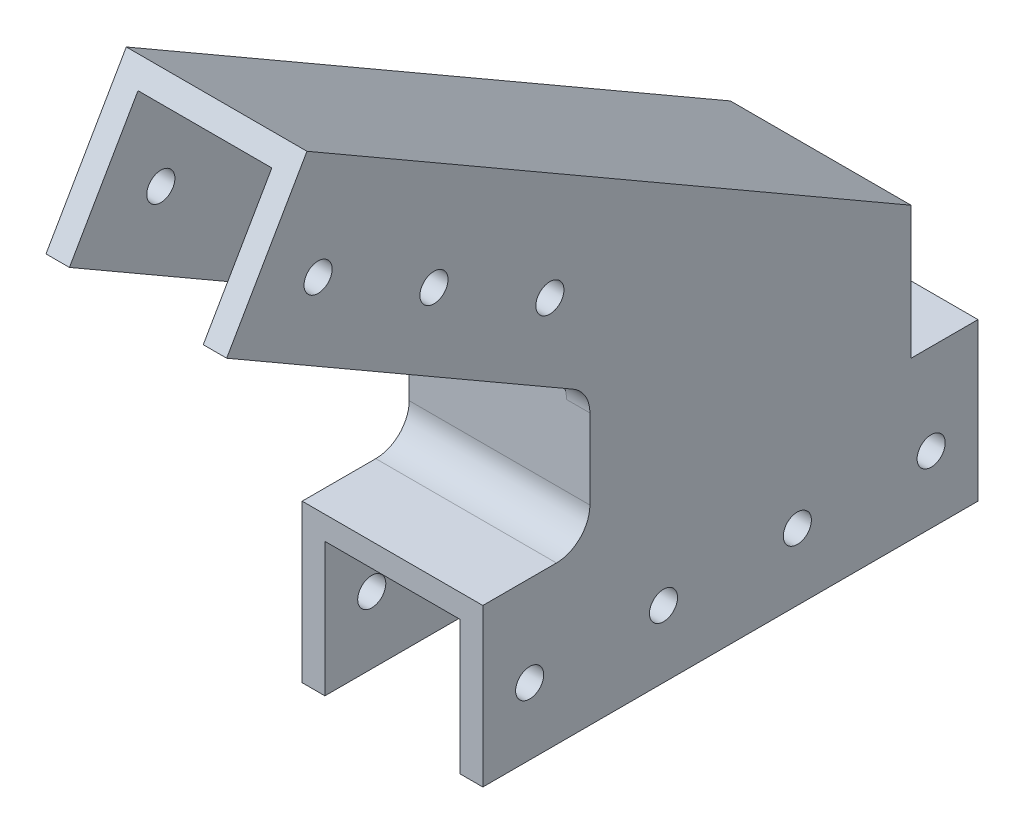
SolidWorks part; units mm, degrees
material "Custom Plastic"
ref_plane "Front Plane" through (0, 0, 0) normal (0, 0, 1) x (1, 0, 0)
ref_plane "Top Plane" through (0, 0, 0) normal (0, 1, 0) x (1, 0, 0)
ref_plane "Right Plane" through (0, 0, 0) normal (1, 0, 0) x (0, 0, -1)
sketch "Sketch1" plane through (0, 0, 0) normal (0, 0, 1) x (1, 0, 0)
  line L1 (-13.5, -12) -> (13.5, -12)
  line L2 (-13.5, -12) -> (-13.5, 12)
  line L3 (-13.5, 12) -> (13.5, 12)
  line L4 (13.5, -12) -> (13.5, 12)
  line L5 (-13.5, -12) -> (13.5, 12) construction
  line L6 (-13.5, 12) -> (13.5, -12) construction
  point P0 (0, 0)
  dimension "D1" = 27
  dimension "D2" = 24
extrude "Boss-Extrude1" add sketch "Sketch1" along normal mid plane 74
shell "Shell1" thickness 3.5 removed face at (0, 0, -37) removed face at (0, -12, 0) removed face at (0, 0, 37)
sketch "Sketch2" plane through (-13.5, 0, 0) normal (-1, 0, 0) x (0, 0, 1)
  line L0 (-27, 31.8) -> (63.282, 83.9244)
  line L1 (37, 12) -> (-37, 12) construction
  line L2 (63.282, 83.9244) -> (75.282, 63.1397)
  line L3 (75.282, 63.1397) -> (21, 31.8)
  line L4 (21, 31.8) -> (-27, 31.8)
  line L5 (69.282, 73.5321) -> (0, 33.5321) construction
  line L6 (-37, 12) -> (-37, -12) construction
  line L7 (-27, 31.8) -> (-27, 12)
  line L8 (-27, 12) -> (21, 12)
  line L9 (21, 12) -> (21, 31.8)
  point P4 (21, 23.663)
  line M5 (37, 12) -> (-37, 12)
  dimension "D1" = 24
  dimension "D2" = 30
  dimension "D3" = 80
  dimension "D4" = 10
  dimension "D5" = 19.8
extrude "Boss-Extrude2" add sketch "Sketch2" against normal up to surface (27 mm away) contours L4 L3 L2 L0 | L9 L4 L7 M5 region at (-13.5, 53.0973, 31.8959) region at (-13.5, 21.9, -3) up to face at (13.5, 0, 0)
shell "Shell2" thickness 3.5 removed face at (0, 47.4699, 48.141) removed face at (0, 73.5321, 69.282)
sketch "Sketch3" plane through (-13.5, 0, 0) normal (-1, 0, 0) x (0, 0, 1)
  line L0 (-37, -1.5) -> (37, -1.5) construction
  line L1 (-37, 12) -> (-37, -12) construction
  line L2 (37, 12) -> (37, -12) construction
  line L3 (37, -12) -> (-37, -12) construction
  circle A0 centre (-30, -1.5) radius 2.1
  circle A1 centre (-10, -1.5) radius 2.1
  circle A2 centre (10, -1.5) radius 2.1
  circle A3 centre (30, -1.5) radius 2.1
  dimension "D2" = 7
  dimension "D3" = 4.2
  dimension "D5" = 20
  dimension "D1" = 10.5
  dimension "D4" = 4
extrude "Cut-Extrude1" cut sketch "Sketch3" against normal through all
other "Move Face1" flip direction yes face at (10, -1.5, -27.9) face at (-10, -1.5, -32.1) offset 0.1 parameters "D1"=0.1
sketch "Sketch4" plane through (-13.5, 0, 0) normal (-1, 0, 0) x (0, 0, 1)
  line L0 (70.1987, 71.7519) -> (-74.8638, -12) construction
  line L2 (37, -12) -> (-37, -12) construction
  line L4 (-27, 31.8) -> (63.282, 83.9244) construction
  line L5 (75.282, 63.1397) -> (21, 31.8) construction
  line L6 (63.282, 83.9244) -> (75.282, 63.1397) construction
  circle A0 centre (61.6218, 66.8) radius 2.1
  circle A1 centre (44.3013, 56.8) radius 2.1
  circle A2 centre (26.9808, 46.8) radius 2.1
  point P2 (67.0624, 67.7435)
  point P11 (0, 0)
  point P15 (0, 0)
  point P19 (71.4111, 69.6519)
  dimension "D2" = 4.2
  dimension "D3" = 10
  dimension "D5" = 20
  dimension "D1" = 10
  dimension "D4" = 3
extrude "Cut-Extrude2" cut sketch "Sketch4" against normal through all
fillet "Fillet1" radius 5 3 edges at (11.75, 31.8, 21) (-11.75, 31.8, 21) (0, 12, 21)
sketch "Sketch5" plane through (-13.5, 0, 0) normal (-1, 0, 0) x (0, 0, 1)
  line L0 (37, 12) -> (37, -12) construction
  line L1 (-37, -12) -> (37, -12)
  line L2 (-37, -12) -> (-37, -11.5)
  line L3 (-37, -11.5) -> (37, -11.5)
  line L4 (37, -12) -> (37, -11.5)
  dimension "D1" = 0.5
extrude "Cut-Extrude3" cut sketch "Sketch5" against normal through all
